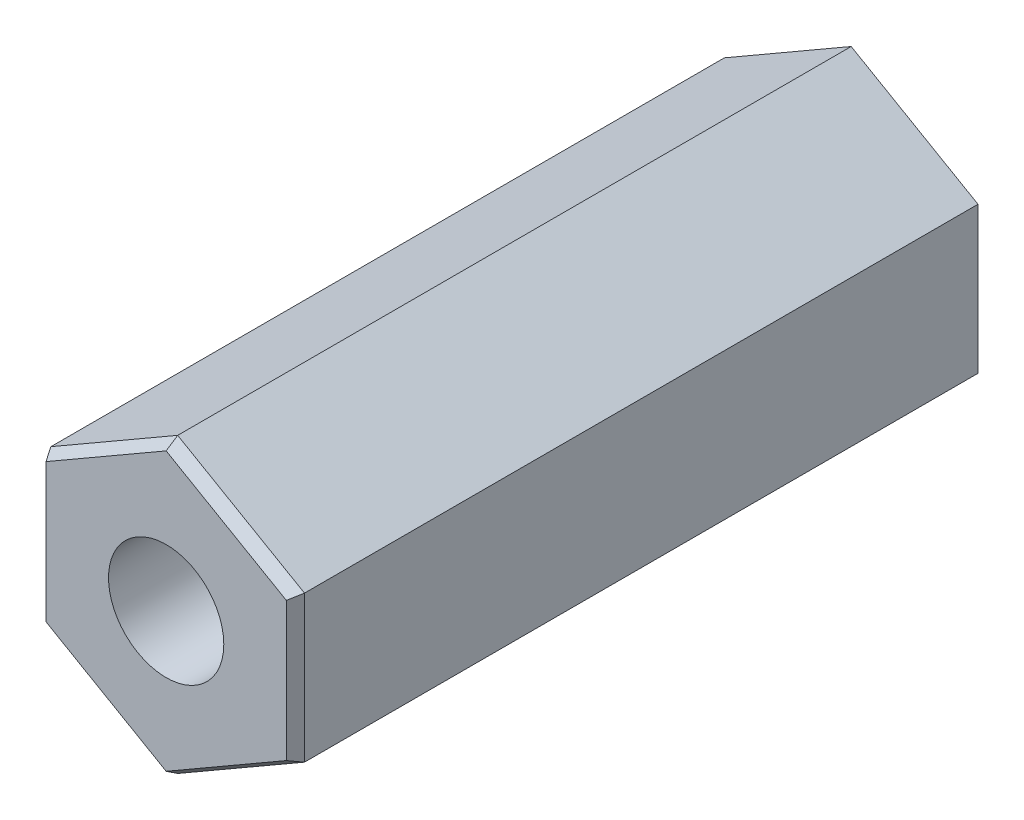
SolidWorks part; units mm, degrees
material "KS26"
ref_plane "正面" through (0, 0, 0) normal (0, 0, 1) x (1, 0, 0)
ref_plane "平面" through (0, 0, 0) normal (0, 1, 0) x (1, 0, 0)
ref_plane "右側面" through (0, 0, 0) normal (1, 0, 0) x (0, 0, -1)
sketch "ｽｹｯﾁ1" plane through (0, 0, 0) normal (0, 0, 1) x (1, 0, 0)
  line L1 (-2.75, 1.5877) -> (-2.75, -1.5877)
  line L2 (-2.75, -1.5877) -> (0, -3.1754)
  line L3 (0, -3.1754) -> (2.75, -1.5877)
  line L4 (2.75, -1.5877) -> (2.75, 1.5877)
  line L5 (2.75, 1.5877) -> (0, 3.1754)
  line L6 (0, 3.1754) -> (-2.75, 1.5877)
  circle A0 centre (0, 0) radius 2.75 construction
  dimension "D1" = 5.5
extrude "ﾎﾞｽ - 押し出し1" add sketch "ｽｹｯﾁ1" along normal mid plane 15
hole_wizard "M3 ねじ穴1" positions "ｽｹｯﾁ2" profile "ｽｹｯﾁ3" tap size "M3" standard "JIS" end condition through all
sketch "ｽｹｯﾁ2" plane through (0, 0, 7.5) normal (0, 0, 1) x (1, 0, 0)
  point P0 (0, 0)
cosmetic thread "穴のねじ山1" parameters "D2"=3
sketch "ｽｹｯﾁ3" plane through (0, 0, 7.5) normal (1, 0, 0) x (0, -1, 0)
  line L0 (0, 0) -> (0, 15)
  line L1 (0, 15) -> (1.25, 15)
  line L2 (1.25, 15) -> (1.25, 0)
  line L5 (1.25, 0) -> (0, 0)
  line L11 (0, -6.35) -> (0, 107.95) construction
  dimension "次ｻｰﾌｪｽまでのねじ下穴ﾄﾞﾘﾙ直径" = 2.5
  dimension "次ｻｰﾌｪｽまでのねじ下穴ﾄﾞﾘﾙの深さ" = 15
sketch "ｽｹｯﾁ4" plane through (0, 0, -7.5) normal (0, 0, -1) x (-1, 0, 0)
  circle A0 centre (0, 0) radius 1.5
  dimension "D1" = 3
extrude "ﾎﾞｽ - 押し出し2" [suppressed] add sketch "ｽｹｯﾁ4" along normal blind 6
chamfer "面取り1" [suppressed] distance 0.25 angle 45
chamfer "面取り2" distance 0.25 angle 30 12 edges at (-1.375, 2.3816, 7.5) (1.375, 2.3816, 7.5) (2.75, 0, 7.5) (1.375, -2.3816, 7.5) (-1.375, -2.3816, 7.5) (-2.75, 0, 7.5) (2.75, 0, -7.5) (1.375, -2.3816, -7.5) (-1.375, -2.3816, -7.5) (-2.75, 0, -7.5) (-1.375, 2.3816, -7.5) (1.375, 2.3816, -7.5) first distance on face at (-1.375, 2.3816, 0) first distance on face at (1.375, 2.3816, 0) first distance on face at (2.75, 0, 0) first distance on face at (1.375, -2.3816, 0) first distance on face at (-1.375, -2.3816, 0) first distance on face at (-2.75, 0, 0) first distance on face at (1.25, 0, -7.5)
